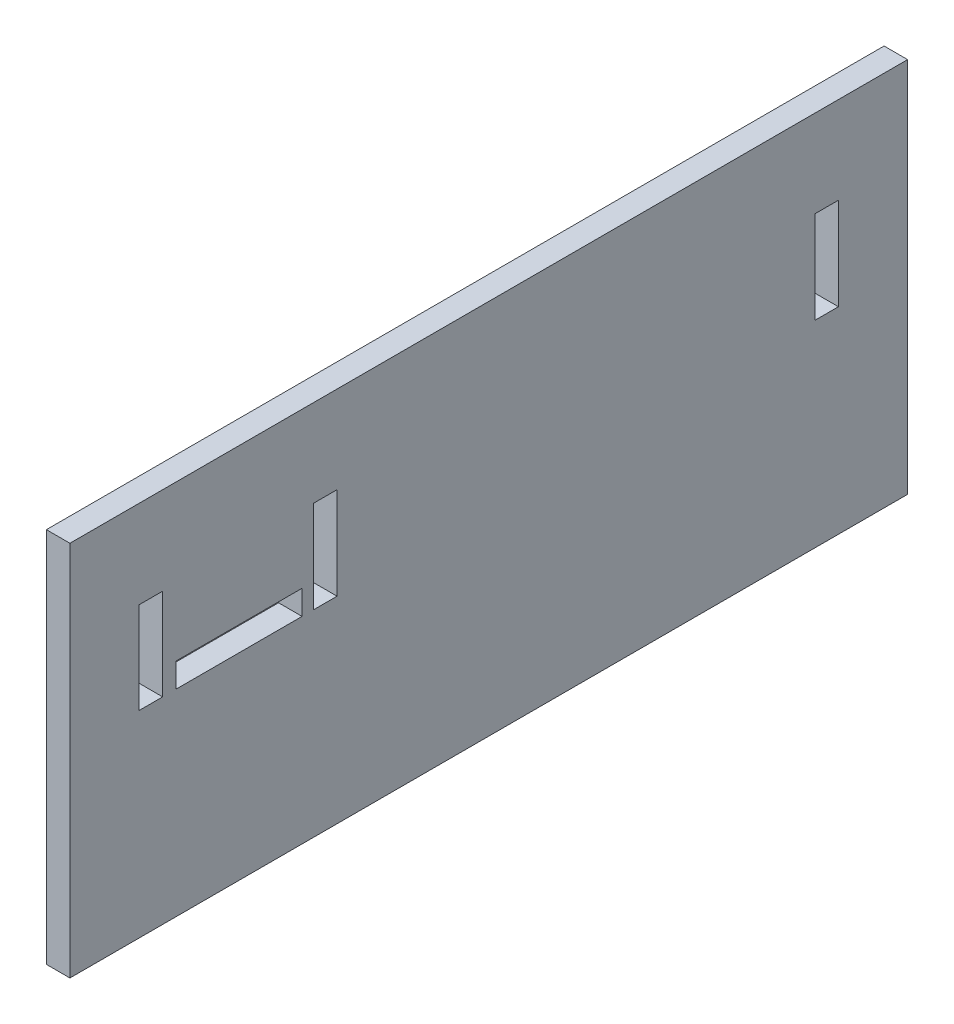
SolidWorks part; units mm, degrees
ref_plane "Front Plane" through (0, 0, 0) normal (0, 0, 1) x (1, 0, 0)
ref_plane "Top Plane" through (0, 0, 0) normal (0, 1, 0) x (1, 0, 0)
ref_plane "Right Plane" through (0, 0, 0) normal (1, 0, 0) x (0, 0, -1)
sketch "Sketch1" plane through (0, 0, 0) normal (1, 0, 0) x (0, 0, -1)
  line L0 (6.775, 20.4226) -> (9.475, 20.4226) construction
  line L1 (6.775, 9.9226) -> (9.475, 9.9226)
  line L2 (9.475, 9.9226) -> (9.475, 20.4226)
  line L3 (9.475, 20.4226) -> (6.775, 20.4226)
  line L4 (6.775, 9.9226) -> (9.475, 9.9226) construction
  line L5 (3.2125, 30.5) -> (83.4125, 30.5)
  line L7 (86.975, 20.5018) -> (84.275, 20.5018)
  line L8 (84.275, 20.5018) -> (84.275, 9.9226)
  line L9 (84.275, 9.9226) -> (86.975, 9.9226)
  line L10 (10.986, 12.7166) -> (25.464, 12.7166)
  line L11 (86.975, -12.68) -> (6.775, -12.68)
  line L12 (10.986, 12.7166) -> (10.986, 9.9226)
  line L13 (26.775, 20.5018) -> (29.475, 20.5018)
  line L14 (26.775, 20.5018) -> (26.775, 9.9226)
  line L15 (26.775, 9.9226) -> (29.475, 9.9226)
  line L16 (29.475, 20.5018) -> (29.475, 9.9226)
  line L17 (3.2125, 30.5) -> (-1.1625, 30.5)
  line L18 (6.775, 20.4226) -> (6.775, 9.9226)
  line L19 (6.775, -12.68) -> (-1.1625, -12.68)
  line L20 (-1.1625, 30.5) -> (-1.1625, -12.68)
  line L21 (83.4125, 30.5) -> (94.9125, 30.5)
  line L22 (86.975, 20.5018) -> (86.975, 9.9226)
  line L23 (86.975, -12.68) -> (94.9125, -12.68)
  line L24 (94.9125, 30.5) -> (94.9125, -12.68)
  line L25 (10.986, 9.9226) -> (25.464, 9.9226)
  line L26 (25.464, 12.7166) -> (25.464, 9.9226)
  line L28 (26.775, 20.5018) -> (29.475, 20.5018) construction
  point P18 (28.125, 9.9226)
  point P19 (8.125, 9.9226)
  point P20 (85.625, 9.9226)
  dimension "D1" = 2.7
  dimension "D2" = 43.18
  dimension "D4" = 7.9375
  dimension "D5" = 20
  dimension "D6" = 57.5
  dimension "D7" = 7.9375
extrude "Panel" add sketch "Sketch1" along normal blind 2.7
